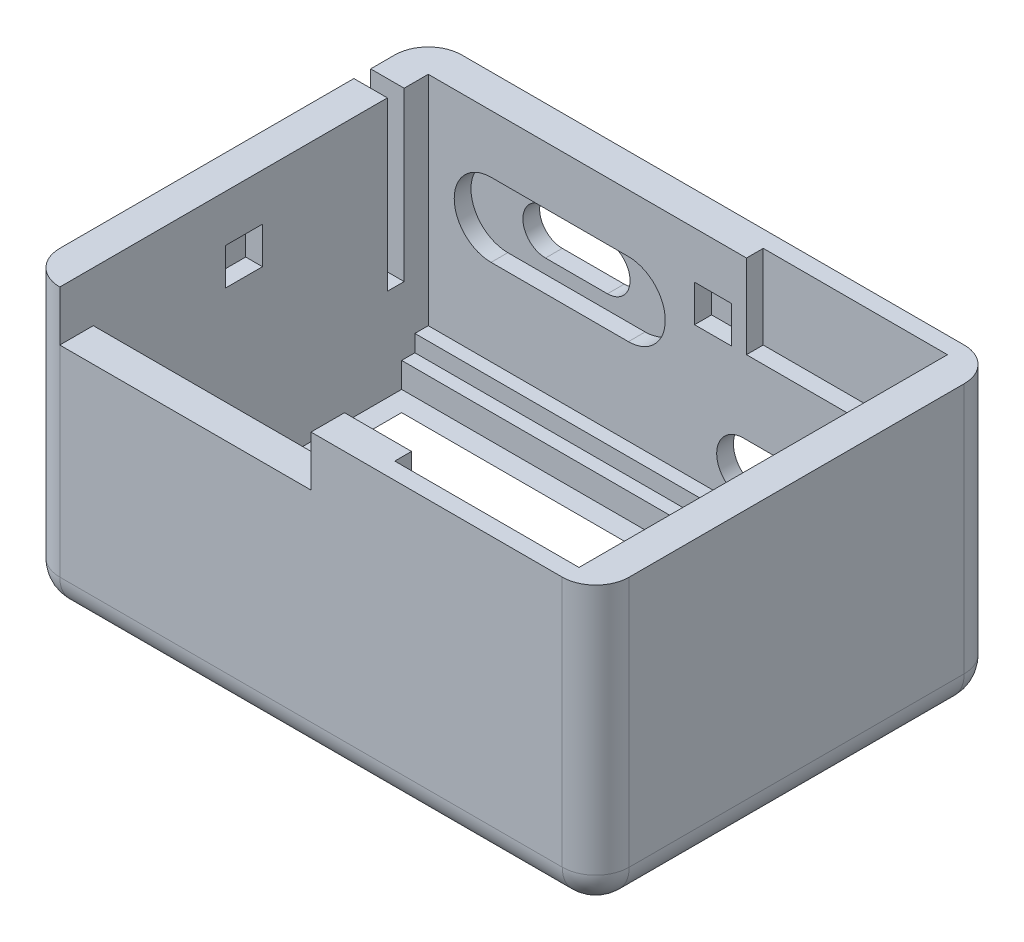
SolidWorks part; units mm, degrees
ref_plane "前视基准面" through (0, 0, 0) normal (0, 0, 1) x (1, 0, 0)
ref_plane "上视基准面" through (0, 0, 0) normal (0, 1, 0) x (1, 0, 0)
ref_plane "右视基准面" through (0, 0, 0) normal (1, 0, 0) x (0, 0, -1)
sketch "草图1" plane through (0, 0, 0) normal (0, 1, 0) x (1, 0, 0)
  line L1 (-72.1576, -30.7504) -> (-38.1576, -30.7504)
  line L2 (-72.1576, -30.7504) -> (-72.1576, -6.7504)
  line L3 (-72.1576, -6.7504) -> (-38.1576, -6.7504)
  line L4 (-38.1576, -30.7504) -> (-38.1576, -6.7504)
  dimension "D1" = 24
  dimension "D2" = 34
extrude "凸台-拉伸1" add sketch "草图1" along normal blind 17 contours L2 L1 L4 L3
sketch "草图2" plane through (0, 17, 0) normal (0, 1, 0) x (1, 0, 0)
  line L0 (-38.1576, -30.7504) -> (-38.1576, -6.7504) construction
  line L1 (-70.1576, -8.7504) -> (-40.1576, -8.7504)
  line L2 (-70.1576, -8.7504) -> (-70.1576, -28.7504)
  line L3 (-70.1576, -28.7504) -> (-40.1576, -28.7504)
  line L4 (-40.1576, -8.7504) -> (-40.1576, -28.7504)
  line L5 (-72.1576, -30.7504) -> (-38.1576, -30.7504) construction
  line L6 (-72.1576, -30.7504) -> (-72.1576, -6.7504) construction
  line L7 (-72.1576, -6.7504) -> (-38.1576, -6.7504) construction
  dimension "D1" = 2
  dimension "D2" = 2
  dimension "D3" = 2
  dimension "D4" = 2
extrude "切除-拉伸1" cut sketch "草图2" against normal blind 14
sketch "草图4" plane through (0, 0, 0) normal (0, -1, 0) x (-1, 0, 0)
  line L0 (72.1576, -30.7504) -> (72.1576, -6.7504) construction
  line L1 (68.9576, -11.5404) -> (53.7476, -11.5404)
  line L2 (68.9576, -11.5404) -> (68.9576, -26.7504)
  line L3 (68.9576, -26.7504) -> (53.7476, -26.7504)
  line L4 (53.7476, -11.5404) -> (53.7476, -26.7504)
  line L6 (72.1576, -30.7504) -> (38.1576, -30.7504) construction
  dimension "D1" = 15.21
  dimension "D2" = 15.21
  dimension "D3" = 3.2
  dimension "D4" = 4
extrude "切除-拉伸2" cut sketch "草图4" against normal blind 15 contours L2 L1 L4 L3
sketch "草图5" plane through (0, 0, 6.7504) normal (0, 0, -1) x (-1, 0, 0)
  line L0 (72.1576, 0) -> (38.1576, 0) construction
  line L6 (64.1576, 11.35) -> (60.4576, 11.35) construction
  line L7 (64.1576, 10) -> (60.4576, 10)
  line L8 (64.1576, 12.7) -> (60.4576, 12.7)
  line L9 (72.1576, 17) -> (72.1576, 0) construction
  arc A0 (64.1576, 10) -> (64.1576, 12.7) centre (64.1576, 11.35) ccw
  arc A1 (60.4576, 12.7) -> (60.4576, 10) centre (60.4576, 11.35) ccw
  point P10 (62.3076, 11.35)
  dimension "D3" = 10
  dimension "D2" = 2.7
  dimension "D1" = 8
  dimension "D4" = 3.7
extrude "切除-拉伸3" cut sketch "草图5" against normal blind 15
sketch "草图6" plane through (0, 0, 30.7504) normal (0, 0, 1) x (1, 0, 0)
  line L0 (-72.1576, 0) -> (-38.1576, 0) construction
  line L1 (-55.1576, 14) -> (-70.1576, 14)
  line L2 (-55.1576, 14) -> (-55.1576, 17)
  line L3 (-55.1576, 17) -> (-70.1576, 17)
  line L4 (-70.1576, 14) -> (-70.1576, 17)
  line L5 (-72.1576, 17) -> (-72.1576, 0) construction
  point P6 (-62.6576, 14)
  point P9 (-70.1576, 15.5)
  dimension "D1" = 14
  dimension "D2" = 3
  dimension "D3" = 2
  dimension "D4" = 15
extrude "切除-拉伸4" cut sketch "草图6" against normal blind 5
sketch "草图7" plane through (0, 0, 6.7504) normal (0, 0, -1) x (-1, 0, 0)
  line L0 (72.1576, 0) -> (38.1576, 0) construction
  line L3 (51.3376, 6) -> (45.1376, 6) construction
  line L4 (51.3376, 2.4) -> (45.1376, 2.4)
  line L5 (51.3376, 9.6) -> (45.1376, 9.6)
  line L6 (38.1576, 17) -> (38.1576, 0) construction
  arc A2 (51.3376, 2.4) -> (51.3376, 9.6) centre (51.3376, 6) ccw
  arc A3 (45.1376, 9.6) -> (45.1376, 2.4) centre (45.1376, 6) ccw
  point P2 (41.5376, 6)
  point P10 (48.2376, 6)
  point P15 (48.2376, 9.6)
  dimension "D1" = 2.4
  dimension "D2" = 3.38
  dimension "D3" = 6.2
  dimension "D4" = 7.2
extrude "切除-拉伸7" cut sketch "草图7" against normal blind 1
sketch "草图9" plane through (0, 0, 7.7504) normal (0, 0, -1) x (-1, 0, 0)
  line L0 (51.3376, 6) -> (45.5376, 6) construction
  line L1 (51.3376, 4.4) -> (45.5376, 4.4)
  line L2 (51.3376, 7.6) -> (45.5376, 7.6)
  line L3 (51.3376, 9.6) -> (45.1376, 9.6) construction
  arc A0 (51.3376, 4.4) -> (51.3376, 7.6) centre (51.3376, 6) ccw
  arc A1 (45.5376, 7.6) -> (45.5376, 4.4) centre (45.5376, 6) ccw
  arc A2 (51.3376, 2.4) -> (51.3376, 9.6) centre (51.3376, 6) ccw construction
  point P2 (48.4376, 6)
  point P12 (54.9376, 6)
  point P13 (52.9376, 6)
  point P14 (43.9376, 6)
  dimension "D1" = 2
  dimension "D2" = 2
  dimension "D3" = 3.2
  dimension "D4" = 9
extrude "切除-拉伸8" cut sketch "草图9" against normal blind 1
sketch "草图10" plane through (0, 0, 8.7504) normal (0, 0, 1) x (1, 0, 0)
  line L2 (-66.4076, 11.35) -> (-58.2076, 11.35) construction
  line L3 (-66.4076, 13.55) -> (-58.2076, 13.55)
  line L6 (-66.4076, 9.15) -> (-58.2076, 9.15)
  arc A7 (-66.4076, 13.55) -> (-66.4076, 9.15) centre (-66.4076, 11.35) ccw
  arc A8 (-58.2076, 9.15) -> (-58.2076, 13.55) centre (-58.2076, 11.35) ccw
  arc A9 (-60.4576, 10) -> (-60.4576, 12.7) centre (-60.4576, 11.35) ccw construction
  arc A10 (-64.1576, 12.7) -> (-64.1576, 10) centre (-64.1576, 11.35) ccw construction
  point P2 (0, 0)
  point P5 (0, 0)
  point P7 (-59.1076, 11.35)
  point P8 (-62.3076, 11.35)
  point P13 (0, 0)
  point P17 (-65.5076, 11.35)
  point P18 (0, 0)
  point P21 (-65.5212, 11.303)
  dimension "D2" = 0.9
  dimension "D3" = 0.9
  dimension "D1" = 4.4
extrude "切除-拉伸9" cut sketch "草图10" against normal blind 1
sketch "草图11" plane through (0, 3, 0) normal (0, 1, 0) x (1, 0, 0)
  line L0 (-68.9576, -26.7504) -> (-68.9576, -11.5404) construction
  line L1 (-48.1576, -10.3404) -> (-70.1576, -10.3404)
  line L2 (-48.1576, -10.3404) -> (-48.1576, -27.9404)
  line L3 (-48.1576, -27.9404) -> (-70.1576, -27.9404)
  line L4 (-70.1576, -10.3404) -> (-70.1576, -27.9404)
  line L5 (-53.7476, -11.5404) -> (-68.9576, -11.5404) construction
  dimension "D1" = 22
  dimension "D2" = 17.6
  dimension "D3" = 1.2
  dimension "D4" = 1.2
extrude "切除-拉伸10" cut sketch "草图11" against normal blind 1.5
sketch "草图12" plane through (0, 17, 0) normal (0, 1, 0) x (1, 0, 0)
  line L0 (-72.1576, -30.7504) -> (-72.1576, -6.7504) construction
  line L1 (-72.1576, -10.1904) -> (-70.1576, -10.1904)
  line L2 (-72.1576, -10.1904) -> (-72.1576, -11.1904)
  line L3 (-72.1576, -11.1904) -> (-70.1576, -11.1904)
  line L4 (-70.1576, -10.1904) -> (-70.1576, -11.1904)
  line L5 (-70.1576, -8.7504) -> (-70.1576, -30.7504) construction
  line L6 (-72.1576, -6.7504) -> (-38.1576, -6.7504) construction
  dimension "D1" = 1
  dimension "D2" = 3.44
extrude "切除-拉伸11" cut sketch "草图12" against normal blind 10
sketch "草图13" plane through (0, 17, 0) normal (0, 1, 0) x (1, 0, 0)
  line L6 (-55.1576, -28.7504) -> (-40.1576, -28.7504) construction
  line L7 (-51.1576, -28.7504) -> (-40.1576, -28.7504)
  line L8 (-51.1576, -28.7504) -> (-51.1576, -29.7504)
  line L9 (-51.1576, -29.7504) -> (-40.1576, -29.7504)
  line L10 (-40.1576, -28.7504) -> (-40.1576, -29.7504)
  line L11 (-40.1576, -8.7504) -> (-70.1576, -8.7504) construction
  line L12 (-51.1576, -8.7504) -> (-40.1576, -8.7504)
  line L13 (-51.1576, -8.7504) -> (-51.1576, -7.7504)
  line L14 (-51.1576, -7.7504) -> (-40.1576, -7.7504)
  line L15 (-40.1576, -8.7504) -> (-40.1576, -7.7504)
  line L16 (-40.1576, -28.7504) -> (-40.1576, -8.7504) construction
  dimension "D1" = 1
  dimension "D2" = 1
  dimension "D3" = 11
extrude "切除-拉伸12" cut sketch "草图13" against normal blind 5
fillet "圆角2" radius 2 8 edges at (-38.1576, 8.5, 6.7504) (-55.1576, 0, 6.7504) (-55.1576, 0, 30.7504) (-72.1576, 0, 18.7504) (-72.1576, 8.5, 30.7504) (-38.1576, 8.5, 30.7504) (-38.1576, 0, 18.7504) (-72.1576, 8.5, 6.7504)
sketch "草图14" plane through (0, 3, 0) normal (0, 1, 0) x (1, 0, 0)
  line L0 (-40.1576, -28.7504) -> (-40.1576, -8.7504) construction
  line L1 (-45.4076, -19.2204) -> (-43.3076, -19.2204)
  line L2 (-45.4076, -19.2204) -> (-45.4076, -23.4304)
  line L3 (-45.4076, -23.4304) -> (-43.3076, -23.4304)
  line L4 (-43.3076, -19.2204) -> (-43.3076, -23.4304)
  line L5 (-70.1576, -28.7504) -> (-40.1576, -28.7504) construction
  point P6 (-44.3576, -23.4304)
  dimension "D1" = 3.15
  dimension "D2" = 5.32
  dimension "D3" = 4.21
  dimension "D4" = 2.1
extrude "切除-拉伸13" cut sketch "草图14" against normal blind 1.5
sketch "草图15" plane through (0, 3, 0) normal (0, 1, 0) x (1, 0, 0)
  line L0 (-40.1576, -8.7504) -> (-70.1576, -8.7504) construction
  line L1 (-70.1576, -9.5504) -> (-40.1576, -9.5504)
  line L2 (-70.1576, -9.5504) -> (-70.1576, -8.7504)
  line L3 (-70.1576, -8.7504) -> (-40.1576, -8.7504)
  line L4 (-40.1576, -9.5504) -> (-40.1576, -8.7504)
  line L5 (-40.1576, -28.7504) -> (-40.1576, -8.7504) construction
  line L6 (-70.1576, -8.7504) -> (-70.1576, -10.3404) construction
  dimension "D1" = 0.8
extrude "凸台-拉伸2" add sketch "草图15" along normal blind 1
chamfer "倒角2" distance 1.5 distance2 2 4 edges at (-61.3526, 0, 26.7504) (-53.7476, 0, 19.1454) (-61.3526, 0, 11.5404) (-68.9576, 0, 19.1454) first distance on face at (-61.3526, 0.75, 26.7504) first distance on face at (-53.7476, 0.75, 19.1454) first distance on face at (-61.3526, 0.75, 11.5404) first distance on face at (-68.9576, 0.75, 19.1454)
sketch "草图16" plane through (0, 0, 8.7504) normal (0, 0, 1) x (1, 0, 0)
  line L0 (-51.1576, 17) -> (-70.1576, 17) construction
  line L1 (-54.2576, 14.2) -> (-52.0576, 14.2)
  line L2 (-54.2576, 14.2) -> (-54.2576, 12)
  line L3 (-54.2576, 12) -> (-52.0576, 12)
  line L4 (-52.0576, 14.2) -> (-52.0576, 12)
  line L5 (-51.1576, 12) -> (-51.1576, 17) construction
  dimension "D1" = 2.2
  dimension "D2" = 2.2
  dimension "D3" = 2.8
  dimension "D4" = 0.9
extrude "切除-拉伸14" cut sketch "草图16" against normal blind 1 draft 1 contours L1 L4 L3 L2
sketch "草图18" plane through (0, 0, 28.7504) normal (0, 0, -1) x (-1, 0, 0)
  line L0 (55.1576, 17) -> (51.1576, 17) construction
  line L1 (54.2576, 14.2) -> (52.0576, 14.2)
  line L2 (54.2576, 14.2) -> (54.2576, 12)
  line L3 (54.2576, 12) -> (52.0576, 12)
  line L4 (52.0576, 14.2) -> (52.0576, 12)
  line L5 (51.1576, 12) -> (51.1576, 17) construction
  dimension "D1" = 2.8
  dimension "D2" = 0.9
  dimension "D3" = 2.2
extrude "切除-拉伸15" cut sketch "草图18" against normal blind 1 contours L2 L1 L4 L3
sketch "草图19" plane through (-70.1576, 0, 0) normal (1, 0, 0) x (0, 0, -1)
  line L0 (-11.1904, 17) -> (-30.7504, 17) construction
  line L1 (-20.8504, 14.2) -> (-18.6504, 14.2)
  line L2 (-20.8504, 14.2) -> (-20.8504, 12)
  line L3 (-20.8504, 12) -> (-18.6504, 12)
  line L4 (-18.6504, 14.2) -> (-18.6504, 12)
  line L5 (-30.7504, 17) -> (-30.7504, 14) construction
  dimension "D1" = 2.2
  dimension "D2" = 2.2
  dimension "D3" = 2.8
  dimension "D4" = 9.9
extrude "切除-拉伸16" cut sketch "草图19" against normal blind 1
